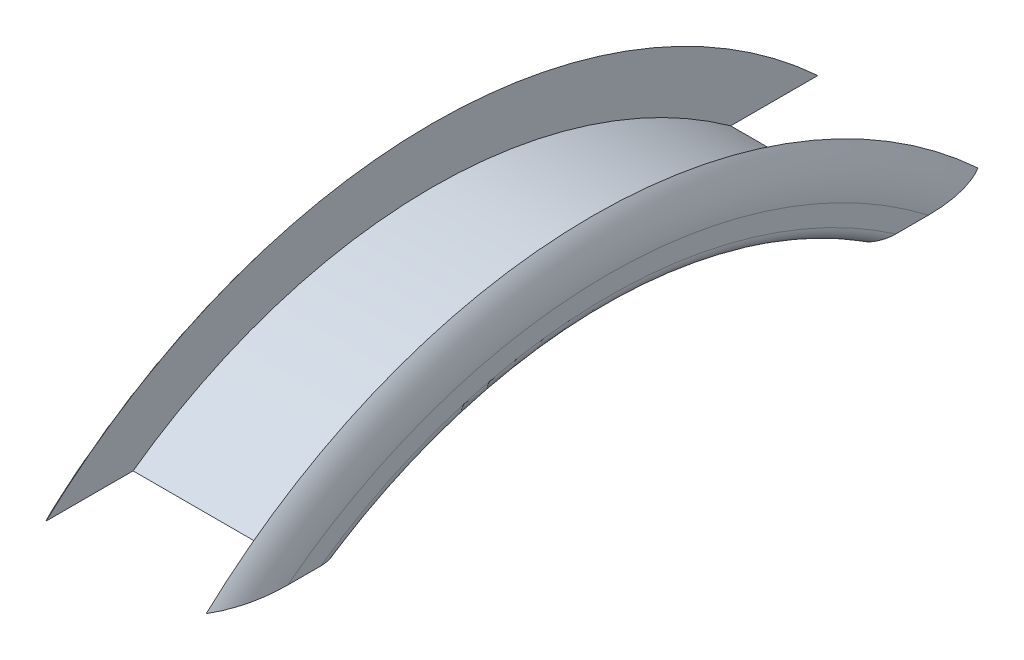
SolidWorks part; units mm, degrees
ref_plane "Спереди" through (0, 0, 0) normal (0, 0, 1) x (1, 0, 0)
ref_plane "Сверху" through (0, 0, 0) normal (0, 1, 0) x (1, 0, 0)
ref_plane "Справа" through (0, 0, 0) normal (1, 0, 0) x (0, 0, -1)
sketch "Эскиз1" plane through (0, 0, 0) normal (0, 0, 1) x (1, 0, 0)
  line L0 (-12.5, 8.6144) -> (-12.5, 0)
  line L1 (12.5, 0) -> (-12.5, 0)
  line L2 (-15, 2) -> (-15, -1)
  line L3 (-13, -3) -> (13, -3)
  line L4 (0, 0) -> (0, -3) construction
  line L5 (15, 2) -> (15, -1)
  line L6 (12.5, 8.6144) -> (12.5, 0)
  line L7 (-34.9588, -80) -> (30.9691, -80) construction
  arc A0 (-12.5, 8.6144) -> (-15, 2) centre (-5, 2) ccw
  arc A1 (-13, -3) -> (-15, -1) centre (-13, -1) cw
  arc A2 (13, -3) -> (15, -1) centre (13, -1) ccw
  arc A3 (12.5, 8.6144) -> (15, 2) centre (5, 2) cw
  dimension "D1" = 2
  dimension "D2" = 10
  dimension "D3" = 5
  dimension "D4" = 2
  dimension "D5" = 3
  dimension "D6" = 25
  dimension "D7" = 80
revolve "Повернуть1" add sketch "Эскиз1" angle 360 about L7
sketch "Эскиз2" plane through (15, 0, 0) normal (1, 0, 0) x (0, 0, -1)
  line L0 (-60.2288, -15) -> (60.2288, -15)
  circle A0 centre (0, -80) radius 88.6144 construction
  circle A1 centre (0, -80) radius 77 construction
  dimension "D1" = 65
extrude "Вырез-Вытянуть1" cut sketch "Эскиз2" against normal through all flip side to cut
